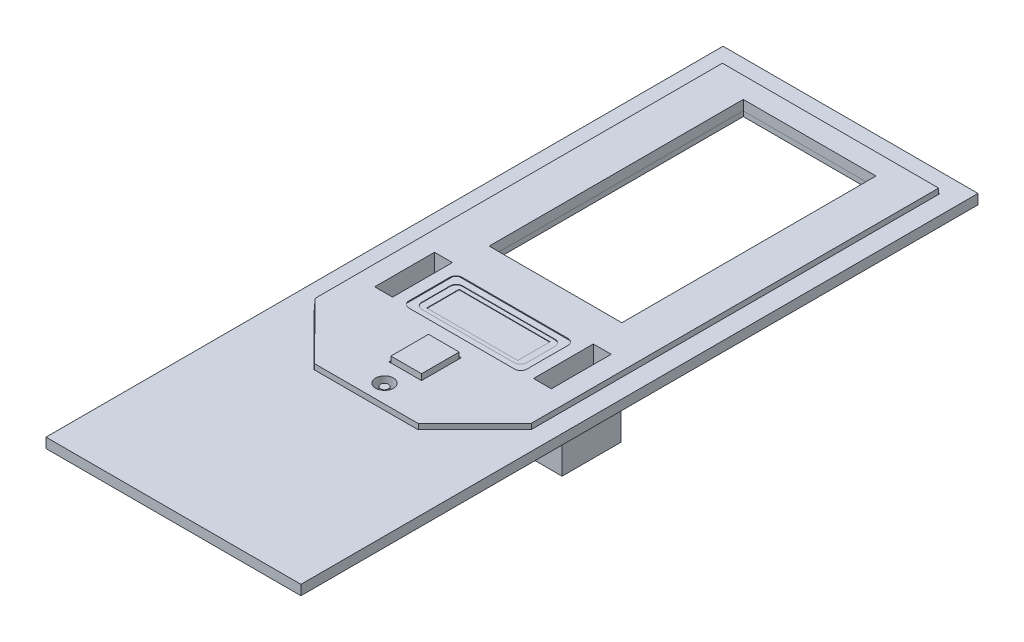
SolidWorks part; units mm, degrees
other "Main"
other "secondary"
other "mainDoorPanel"
other "secondaryPanel"
ref_plane "Front Plane" through (0, 0, 0) normal (0, 0, 1) x (1, 0, 0)
ref_plane "Top Plane" through (0, 0, 0) normal (0, 1, 0) x (1, 0, 0)
ref_plane "Right Plane" through (0, 0, 0) normal (1, 0, 0) x (0, 0, -1)
sketch "Sketch1" plane through (0, 0, 0) normal (0, 1, 0) x (1, 0, 0)
  line L1 (-31.4334, 64.5752) -> (19.899, 64.5752)
  line L2 (-31.4334, 64.5752) -> (-31.4334, -71.7502)
  line L3 (-31.4334, -71.7502) -> (19.899, -71.7502)
  line L4 (19.899, 64.5752) -> (19.899, -71.7502)
  dimension "D1" = 136.3254
  dimension "D2" = 51.3324
extrude "Boss-Extrude1" add sketch "Sketch1" along normal blind 2
sketch "Sketch2" plane through (0, 2, 0) normal (0, 1, 0) x (1, 0, 0)
  line L2 (-27.5414, -30.4459) -> (-27.5414, 60.5429)
  line L3 (-27.5414, 60.5429) -> (16.007, 60.5429)
  line L4 (16.007, -30.4459) -> (16.007, 60.5429)
  line L5 (19.899, -71.7502) -> (19.899, 64.5752) construction
  line L6 (-31.4334, 64.5752) -> (-31.4334, -71.7502) construction
  line L7 (19.899, 64.5752) -> (-31.4334, 64.5752) construction
  line L8 (-16.2134, -41.6661) -> (4.679, -41.6661)
  line L9 (16.007, -30.4459) -> (4.679, -41.6661)
  line L10 (-16.2134, -41.6661) -> (-27.5414, -30.4459)
  dimension "D2" = 3.892
  dimension "D3" = 3.892
  dimension "D4" = 43.5484
  dimension "D5" = 4.0323
  dimension "D6" = 15.22
  dimension "D8" = 15.22
extrude "Cut-Extrude1" cut sketch "Sketch2" against normal blind 1
sketch "Sketch3" plane through (0, 1, 0) normal (0, 1, 0) x (1, 0, 0)
  line L1 (-19.1263, 56.3354) -> (7.5918, 56.3354)
  line L2 (-19.1263, 56.3354) -> (-19.1263, 5.1745)
  line L3 (-19.1263, 5.1745) -> (7.5918, 5.1745)
  line L4 (7.5918, 56.3354) -> (7.5918, 5.1745)
extrude "Cut-Extrude2" cut sketch "Sketch3" against normal blind 1
sketch "Sketch4" plane through (0, 1, 0) normal (0, 1, 0) x (1, 0, 0)
  line L0 (-19.1263, 5.1745) -> (7.5918, 5.1745) construction
  line L1 (-16.0968, -1.1859) -> (4.5624, -1.1859)
  line L2 (-16.0968, -1.1859) -> (-16.0968, -14.7904)
  line L3 (-16.0968, -14.7904) -> (4.5624, -14.7904)
  line L4 (4.5624, -1.1859) -> (4.5624, -14.7904)
  dimension "D1" = 13.6045
  dimension "D2" = 20.6592
  dimension "D3" = 6.3604
extrude "Boss-Extrude2" add sketch "Sketch4" along normal blind 1
sketch "Sketch5" plane through (0, 1, 0) normal (0, 1, 0) x (1, 0, 0)
  line L0 (-27.5414, 60.5429) -> (-27.5414, -30.4459) construction
  line L1 (-18.4951, 0) -> (-25.0169, 0)
  line L2 (-18.4951, 0) -> (-18.4951, -14.8535)
  line L3 (-18.4951, -14.8535) -> (-25.0169, -14.8535)
  line L4 (-25.0169, 0) -> (-25.0169, -14.8535)
  line L5 (6.9607, -14.8535) -> (13.4824, -14.8535)
  line L6 (6.9607, -14.8535) -> (6.9607, 0.7912)
  line L7 (6.9607, 0.7912) -> (13.4824, 0.7912)
  line L8 (13.4824, -14.8535) -> (13.4824, 0.7912)
  line L9 (16.007, -30.4459) -> (16.007, 60.5429) construction
  line L10 (-16.0968, -14.7904) -> (4.5624, -14.7904) construction
  dimension "D1" = 6.5217
  dimension "D2" = 6.5217
  dimension "D3" = 2.5245
  dimension "D4" = 2.5245
  dimension "D5" = 0.0631
  dimension "D6" = 0.0631
extrude "Cut-Extrude3" cut sketch "Sketch5" against normal blind 1
sketch "Sketch6" plane through (0, 1, 0) normal (0, 1, 0) x (1, 0, 0)
  line L0 (-5.7672, -14.7904) -> (-5.7672, -41.6661) construction
  line L1 (-8.8528, -17.315) -> (-2.6817, -17.315)
  line L2 (-8.8528, -17.315) -> (-8.8528, -24.8886)
  line L3 (-8.8528, -24.8886) -> (-2.6817, -24.8886)
  line L4 (-2.6817, -17.315) -> (-2.6817, -24.8886)
  line L5 (-16.0968, -14.7904) -> (4.5624, -14.7904) construction
  line L6 (-16.2134, -41.6661) -> (4.679, -41.6661) construction
  line L7 (-16.0968, -14.7904) -> (4.5624, -14.7904) construction
  dimension "D1" = 7.5736
  dimension "D2" = 6.1711
  dimension "D3" = 3.0856
  dimension "D4" = 2.5245
extrude "Cut-Extrude4" cut sketch "Sketch6" against normal blind 1
sketch "Sketch7" plane through (0, 1, 0) normal (0, 1, 0) x (1, 0, 0)
  line L0 (-8.8528, -24.8886) -> (-2.6817, -24.8886) construction
  circle A0 centre (-5.7672, -29.2505) radius 2.4895
  dimension "D1" = 4.3619
extrude "Cut-Extrude5" cut sketch "Sketch7" against normal blind 1
sketch "Sketch8" plane through (0, 1, 0) normal (0, 1, 0) x (1, 0, 0)
  line L6 (-27.5414, -21.4805) -> (-27.5414, -30.4459)
  line L8 (-27.5414, -30.4459) -> (-16.2134, -41.6661)
  line L10 (-16.2134, -41.6661) -> (4.679, -41.6661)
  line L16 (4.679, -41.6661) -> (16.007, -30.4459)
  line L18 (16.007, -30.4459) -> (16.007, -21.4805)
  line L22 (4.6739, -32.9033) -> (16.007, -21.4805)
  line L23 (16.007, -30.4459) -> (16.007, 60.5429) construction
  line L24 (-16.2083, -32.9033) -> (-27.5414, -21.4805)
  line L25 (-27.5414, 60.5429) -> (-27.5414, -30.4459) construction
  line L26 (4.6739, -32.9033) -> (-16.2083, -32.9033)
extrude "Boss-Extrude3" add sketch "Sketch8" along normal blind 1
sketch "Sketch9" plane through (0, 1, 0) normal (0, 1, 0) x (1, 0, 0)
  line L1 (-8.8528, -24.8886) -> (-2.6817, -24.8886)
  line L2 (-8.8528, -24.8886) -> (-8.8528, -17.315)
  line L3 (-8.8528, -17.315) -> (-2.6817, -17.315)
  line L4 (-2.6817, -24.8886) -> (-2.6817, -17.315)
sketch "Sketch10" plane through (0, 0, 0) normal (0, -1, 0) x (1, 0, 0)
  line L1 (-8.8528, 24.8886) -> (-2.6817, 24.8886)
  line L2 (-8.8528, 24.8886) -> (-8.8528, 17.315)
  line L3 (-8.8528, 17.315) -> (-2.6817, 17.315)
  line L4 (-2.6817, 24.8886) -> (-2.6817, 17.315)
extrude "Boss-Extrude4" add sketch "Sketch10" against normal blind 4
sketch "Sketch11" plane through (0, 1, 0) normal (0, 1, 0) x (1, 0, 0)
  line L0 (-27.5414, 60.5429) -> (16.007, 60.5429)
  line L1 (16.007, 60.5429) -> (16.007, -21.4805)
  line L2 (16.007, -21.4805) -> (4.6739, -32.9033)
  line L3 (4.6739, -32.9033) -> (-16.2083, -32.9033)
  line L4 (-16.2083, -32.9033) -> (-27.5414, -21.4805)
  line L5 (-27.5414, -21.4805) -> (-27.5414, 60.5429)
extrude "Boss-Extrude5" add sketch "Sketch11" along normal blind 2 separate body
sketch "Sketch12" plane through (0, 3, 0) normal (0, 1, 0) x (1, 0, 0)
  line L0 (-8.8528, -17.315) -> (-2.6817, -17.315) construction
  line L1 (-9.0528, -17.115) -> (-2.4817, -17.115)
  line L2 (-9.0528, -17.115) -> (-9.0528, -25.0886)
  line L3 (-9.0528, -25.0886) -> (-2.4817, -25.0886)
  line L4 (-2.4817, -17.115) -> (-2.4817, -25.0886)
  line L5 (-8.8528, -24.8886) -> (-8.8528, -17.315) construction
  line L6 (-2.6817, -24.8886) -> (-8.8528, -24.8886) construction
  line L7 (-2.6817, -17.315) -> (-2.6817, -24.8886) construction
  dimension "D1" = 0.2
  dimension "D2" = 0.2
  dimension "D3" = 0.2
  dimension "D4" = 0.2
extrude "Cut-Extrude6" cut sketch "Sketch12" against normal blind 2
sketch "Sketch13" plane through (0, 1, 0) normal (0, -1, 0) x (1, 0, 0)
  line L1 (-19.1263, -5.1745) -> (7.5918, -5.1745)
  line L2 (-19.1263, -5.1745) -> (-19.1263, -56.3354)
  line L3 (-19.1263, -56.3354) -> (7.5918, -56.3354)
  line L4 (7.5918, -5.1745) -> (7.5918, -56.3354)
  circle A0 centre (-5.7672, 29.2505) radius 1.8
extrude "Cut-Extrude9" cut sketch "Sketch13" against normal blind 2
sketch "Sketch14" plane through (0, 1, 0) normal (0, -1, 0) x (1, 0, 0)
  circle A0 centre (-5.7672, 29.2505) radius 2.2
  circle A1 centre (-5.7672, 29.2505) radius 1.8
extrude "Boss-Extrude11" add sketch "Sketch14" along normal blind 2 separate body
combine bodies "Combine1" operation type add bodies to combine 120 114
sketch "Sketch17" plane through (0, -1, 0) normal (0, -1, 0) x (1, 0, 0)
  circle A0 centre (-5.7672, 29.2505) radius 2.2
extrude "Boss-Extrude12" add sketch "Sketch17" along normal blind 1
sketch "Sketch18" plane through (0, -1, 0) normal (0, 1, 0) x (1, 0, 0)
  circle A0 centre (-5.7672, -29.2505) radius 0.8
extrude "Boss-Extrude15" add sketch "Sketch18" along normal blind 3.4 separate body
combine bodies "Combine3" operation type add bodies to combine 122 126
sketch "Sketch20" plane through (0, 1, 0) normal (0, -1, 0) x (1, 0, 0)
  line L0 (-21.756, 14.8535) -> (-21.756, 0) construction
  line L1 (-24.556, 14.4535) -> (-18.956, 14.4535)
  line L2 (-24.556, 14.4535) -> (-24.556, 0.4)
  line L3 (-24.556, 0.4) -> (-18.956, 0.4)
  line L4 (-18.956, 14.4535) -> (-18.956, 0.4)
  line L5 (7.4216, -0.3912) -> (13.0216, -0.3912)
  line L6 (7.4216, -0.3912) -> (7.4216, 14.4535)
  line L7 (7.4216, 14.4535) -> (13.0216, 14.4535)
  line L8 (13.0216, -0.3912) -> (13.0216, 14.4535)
  line L9 (-25.0169, 14.8535) -> (-18.4951, 14.8535) construction
  line L10 (-18.4951, 0) -> (-25.0169, 0) construction
  line L11 (10.2216, 14.8535) -> (10.2216, -0.7912) construction
  line L12 (6.9607, 14.8535) -> (13.4824, 14.8535) construction
  line L13 (13.4824, -0.7912) -> (6.9607, -0.7912) construction
  dimension "D1" = 2.8
  dimension "D2" = 2.8
  dimension "D3" = 2.8
  dimension "D4" = 2.8
  dimension "D5" = 0.4
  dimension "D6" = 0.4
  dimension "D7" = 0.4
  dimension "D8" = 0.4
extrude "Extrude-Thin3" add sketch "Sketch20" along normal blind 13.324 separate body thin thin type one direction reverse wall 1
sketch "Sketch26" plane through (0, 1, 0) normal (0, -1, 0) x (1, 0, 0)
  line L1 (-23.556, 13.4535) -> (-19.956, 13.4535)
  line L2 (-23.556, 13.4535) -> (-23.556, 1.4)
  line L3 (-23.556, 1.4) -> (-19.956, 1.4)
  line L4 (-19.956, 13.4535) -> (-19.956, 1.4)
  line L5 (8.4216, 0.6088) -> (12.0216, 0.6088)
  line L6 (8.4216, 0.6088) -> (8.4216, 13.4535)
  line L7 (8.4216, 13.4535) -> (12.0216, 13.4535)
  line L8 (12.0216, 0.6088) -> (12.0216, 13.4535)
extrude "Cut-Extrude12" cut sketch "Sketch26" against normal blind 13.324
sketch "Sketch27" plane through (0, -12.324, 0) normal (0, -1, 0) x (1, 0, 0)
  line L0 (7.4216, -0.3912) -> (13.0216, -0.3912) construction
  line L1 (-24.556, 14.4535) -> (-18.956, 14.4535)
  line L2 (-24.556, 14.4535) -> (-24.556, 0.4)
  line L3 (-24.556, 0.4) -> (-18.956, 0.4)
  line L4 (-18.956, 14.4535) -> (-18.956, 0.4)
  line L5 (7.4216, 14.4535) -> (12.992, 14.4535)
  line L6 (7.4216, 14.4535) -> (7.4216, -0.3912)
  line L7 (7.4216, -0.3912) -> (12.992, -0.3912)
  line L8 (12.992, 14.4535) -> (12.992, -0.3912)
extrude "Boss-Extrude18" add sketch "Sketch27" against normal blind 1 separate body
combine bodies "Combine4" operation type add bodies to combine 134 135 136 137 138
sketch "Sketch28" plane through (0, 2, 0) normal (0, 1, 0) x (1, 0, 0)
  line L1 (-16.0968, -1.1859) -> (4.5624, -1.1859)
  line L2 (-16.0968, -1.1859) -> (-16.0968, -14.7904)
  line L3 (-16.0968, -14.7904) -> (4.5624, -14.7904)
  line L4 (4.5624, -1.1859) -> (4.5624, -14.7904)
extrude "Cut-Extrude13" cut sketch "Sketch28" against normal up to surface (1 mm away) up to face at (-5.7672, 1, 31.7399)
sketch "Sketch29" plane through (0, 3, 0) normal (0, 1, 0) x (1, 0, 0)
  line L0 (8.4216, -13.4535) -> (8.4216, -0.6088) construction
  line L1 (-17.656, -2.9778) -> (6.1216, -2.9778)
  line L2 (-17.656, -2.9778) -> (-17.656, -13.706)
  line L3 (-17.656, -13.706) -> (6.1216, -13.706)
  line L4 (6.1216, -2.9778) -> (6.1216, -13.706)
  line L5 (-19.956, -1.4) -> (-19.956, -13.4535) construction
  line L6 (12.0216, -13.4535) -> (8.4216, -13.4535) construction
  line L7 (-23.556, -1.4) -> (-19.956, -1.4) construction
  dimension "D1" = 2.3
  dimension "D2" = 2.3
  dimension "D3" = 0.2525
  dimension "D4" = 1.5778
extrude "Cut-Extrude15" cut sketch "Sketch29" against normal blind 10
sketch "Sketch30" plane through (0, 1, 0) normal (0, 1, 0) x (1, 0, 0)
  line L1 (-17.656, -2.9778) -> (6.1216, -2.9778)
  line L2 (-17.656, -2.9778) -> (-17.656, -13.706)
  line L3 (-17.656, -13.706) -> (6.1216, -13.706)
  line L4 (6.1216, -2.9778) -> (6.1216, -13.706)
  line L5 (-16.3236, -4.2401) -> (4.7892, -4.2401)
  line L6 (-16.3236, -4.2401) -> (-16.3236, -12.4437)
  line L7 (-16.3236, -12.4437) -> (4.7892, -12.4437)
  line L8 (4.7892, -4.2401) -> (4.7892, -12.4437)
  dimension "D1" = 1.3324
  dimension "D2" = 1.3324
  dimension "D3" = 1.2623
  dimension "D4" = 1.2623
extrude "Boss-Extrude20" add sketch "Sketch30" along normal blind 1.8 separate body
sketch "Sketch31" plane through (0, 1, 0) normal (0, 1, 0) x (1, 0, 0)
  line L1 (-16.3236, -4.2401) -> (4.7892, -4.2401)
  line L2 (-16.3236, -4.2401) -> (-16.3236, -12.4437)
  line L3 (-16.3236, -12.4437) -> (4.7892, -12.4437)
  line L4 (4.7892, -4.2401) -> (4.7892, -12.4437)
extrude "Boss-Extrude21" add sketch "Sketch31" along normal blind 1.6 separate body
combine bodies "Combine5" operation type add bodies to combine 140 145 146
sketch "Sketch35" plane through (0, 1, 0) normal (0, -1, 0) x (1, 0, 0)
  line L8 (6.2216, 2.8778) -> (6.2216, 13.806)
  line L9 (6.2216, 13.806) -> (-17.756, 13.806)
  line L10 (-17.756, 13.806) -> (-17.756, 2.8778)
  line L11 (-17.756, 2.8778) -> (6.2216, 2.8778)
  line L12 (6.2216, 2.8778) -> (6.2216, 13.806)
  line L13 (6.2216, 13.806) -> (-17.756, 13.806)
  line L14 (-17.756, 13.806) -> (-17.756, 2.8778)
  line L15 (-17.756, 2.8778) -> (6.2216, 2.8778)
  dimension "D1" = 0.1
extrude "Cut-Extrude21" cut sketch "Sketch35" against normal blind 1.9
fillet "Fillet2" radius 1.25 4 edges at (-17.656, 2.95, 13.706) (6.1216, 2.95, 13.706) (6.1216, 2.95, 2.9778) (-17.656, 2.95, 2.9778)
fillet "Fillet3" radius 1.25 4 edges at (4.7892, 2.7, 12.4437) (4.7892, 2.7, 4.2401) (-16.3236, 2.7, 12.4437) (-16.3236, 2.7, 4.2401)
sketch "Sketch37" plane through (0, 2.6, 0) normal (0, 1, 0) x (1, 0, 0)
  line L4 (3.5392, -4.2401) -> (-15.0736, -4.2401) construction
  line L5 (-14.9211, -5.0781) -> (3.3866, -5.0781)
  line L6 (-14.9211, -5.0781) -> (-14.9211, -11.6057)
  line L7 (-14.9211, -11.6057) -> (3.3866, -11.6057)
  line L8 (3.3866, -5.0781) -> (3.3866, -11.6057)
  line L9 (-16.3236, -5.4901) -> (-16.3236, -11.1937) construction
  line L10 (4.7892, -11.1937) -> (4.7892, -5.4901) construction
  line L11 (-15.0736, -12.4437) -> (3.5392, -12.4437) construction
  dimension "D1" = 0.838
  dimension "D2" = 1.4025
  dimension "D3" = 1.4025
  dimension "D4" = 0.838
extrude "Cut-Extrude22" cut sketch "Sketch37" against normal blind 0.1
sketch "Sketch41" plane through (0, 2.6, 0) normal (0, 1, 0) x (1, 0, 0)
  line L5 (-14.9211, -5.0781) -> (3.3866, -5.0781)
  line L6 (-14.9211, -5.0781) -> (-14.9211, -11.6057)
  line L7 (-14.9211, -11.6057) -> (3.3866, -11.6057)
  line L8 (-15.0736, -12.4437) -> (3.5392, -12.4437)
  line L9 (4.7892, -11.1937) -> (4.7892, -5.4901)
  line L10 (3.5392, -4.2401) -> (-15.0736, -4.2401)
  line L11 (-16.3236, -5.4901) -> (-16.3236, -11.1937)
  line L12 (-15.0736, -12.4437) -> (3.5392, -12.4437)
  line L13 (4.7892, -11.1937) -> (4.7892, -5.4901)
  line L14 (3.5392, -4.2401) -> (-15.0736, -4.2401)
  line L15 (-16.3236, -5.4901) -> (-16.3236, -11.1937)
  line L16 (3.3866, -5.0781) -> (3.3866, -11.6057)
  arc A8 (3.5392, -12.4437) -> (4.7892, -11.1937) centre (3.5392, -11.1937) ccw
  arc A9 (4.7892, -5.4901) -> (3.5392, -4.2401) centre (3.5392, -5.4901) ccw
  arc A10 (-15.0736, -4.2401) -> (-16.3236, -5.4901) centre (-15.0736, -5.4901) ccw
  arc A11 (-16.3236, -11.1937) -> (-15.0736, -12.4437) centre (-15.0736, -11.1937) ccw
  arc A12 (3.5392, -12.4437) -> (4.7892, -11.1937) centre (3.5392, -11.1937) ccw
  arc A13 (4.7892, -5.4901) -> (3.5392, -4.2401) centre (3.5392, -5.4901) ccw
  arc A14 (-15.0736, -4.2401) -> (-16.3236, -5.4901) centre (-15.0736, -5.4901) ccw
  arc A15 (-16.3236, -11.1937) -> (-15.0736, -12.4437) centre (-15.0736, -11.1937) ccw
  dimension "D1" = 0
extrude "Boss-Extrude27" add sketch "Sketch41" along normal blind 0.1 separate body
combine bodies "Combine6" operation type add bodies to combine 160 154
sketch "Sketch43" plane through (0, 2.5, 0) normal (0, 1, 0) x (1, 0, 0)
  line L1 (-14.9211, -5.0781) -> (3.3866, -5.0781)
  line L2 (-14.9211, -5.0781) -> (-14.9211, -11.6057)
  line L3 (-14.9211, -11.6057) -> (3.3866, -11.6057)
  line L4 (3.3866, -5.0781) -> (3.3866, -11.6057)
extrude "Boss-Extrude28" add sketch "Sketch43" along normal blind 0.1 separate body
combine bodies "Combine7" operation type add bodies to combine 162 161
sketch "Sketch50" plane through (13.0216, 0, 0) normal (1, 0, 0) x (0, 0, -1)
  line L0 (-14.4535, 1) -> (-11.2935, -2.16)
  line L1 (0.3912, 1) -> (-14.4535, 1) construction
  line L2 (-14.4535, -12.324) -> (-14.4535, 1) construction
  line L3 (-11.2935, -2.16) -> (-11.2935, -12.324)
  line L4 (0.3912, -12.324) -> (-14.4535, -12.324) construction
  line L5 (-11.2935, -12.324) -> (-14.4535, -12.324)
  line L6 (-14.4535, -12.324) -> (-14.4535, 1)
  dimension "D1" = 3.16
  dimension "D2" = 3.16
extrude "Cut-Extrude24" cut sketch "Sketch50" against normal blind 40.1
sketch "Sketch51" plane through (0, -6.7268, 6.7268) normal (0, -0.7071, 0.7071) x (1, 0, 0)
  line L1 (7.4216, 10.9273) -> (13.0216, 10.9273)
  line L2 (7.4216, 10.9273) -> (7.4216, 6.4584)
  line L3 (7.4216, 6.4584) -> (13.0216, 6.4584)
  line L4 (13.0216, 10.9273) -> (13.0216, 6.4584)
  line L5 (-18.956, 10.9273) -> (-24.556, 10.9273)
  line L6 (-18.956, 10.9273) -> (-18.956, 6.4584)
  line L7 (-18.956, 6.4584) -> (-24.556, 6.4584)
  line L8 (-24.556, 10.9273) -> (-24.556, 6.4584)
extrude "Boss-Extrude29" add sketch "Sketch51" along normal blind 1 separate body
sketch "Sketch52" plane through (0, 7.7268, 7.7268) normal (0, 0.7071, 0.7071) x (1, 0, 0)
  line L1 (7.4216, -9.5131) -> (13.0216, -9.5131)
  line L2 (7.4216, -9.5131) -> (7.4216, -10.5131)
  line L3 (7.4216, -10.5131) -> (13.0216, -10.5131)
  line L4 (13.0216, -9.5131) -> (13.0216, -10.5131)
  line L5 (-24.556, -9.5131) -> (-18.956, -9.5131)
  line L6 (-24.556, -9.5131) -> (-24.556, -10.5131)
  line L7 (-24.556, -10.5131) -> (-18.956, -10.5131)
  line L8 (-18.956, -9.5131) -> (-18.956, -10.5131)
extrude "Boss-Extrude30" add sketch "Sketch52" along normal blind 2.5 separate body
combine bodies "Combine8" operation type add bodies to combine 167 168 169 170 171
sketch "Sketch53" plane through (0, 0, 11.2935) normal (0, 0, 1) x (1, 0, 0)
  line L0 (-24.556, -12.324) -> (-24.556, -2.16) construction
  line L1 (-24.556, -11.324) -> (-18.956, -11.324)
  line L2 (-24.556, -11.324) -> (-24.556, -12.324)
  line L3 (-24.556, -12.324) -> (-18.956, -12.324)
  line L4 (-18.956, -11.324) -> (-18.956, -12.324)
  line L5 (7.4216, -12.324) -> (7.4216, -2.16) construction
  line L6 (13.0216, -12.324) -> (7.4216, -12.324)
  line L7 (13.0216, -12.324) -> (13.0216, -11.324)
  line L8 (13.0216, -11.324) -> (7.4216, -11.324)
  line L9 (7.4216, -12.324) -> (7.4216, -11.324)
  line L10 (8.4216, -11.324) -> (12.0216, -11.324) construction
  line L11 (-23.556, -11.324) -> (-19.956, -11.324) construction
  dimension "D1" = 0
  dimension "D2" = 0
extrude "Boss-Extrude31" add sketch "Sketch53" along normal blind 1
sketch "Sketch54" plane through (0, -11.324, 0) normal (0, 1, 0) x (1, 0, 0)
  line L1 (-24.556, -11.2935) -> (-18.956, -11.2935)
  line L2 (-24.556, -11.2935) -> (-24.556, -12.2935)
  line L3 (-24.556, -12.2935) -> (-18.956, -12.2935)
  line L4 (-18.956, -11.2935) -> (-18.956, -12.2935)
  line L5 (7.4216, -11.2935) -> (13.0216, -11.2935)
  line L6 (7.4216, -11.2935) -> (7.4216, -12.2935)
  line L7 (7.4216, -12.2935) -> (13.0216, -12.2935)
  line L8 (13.0216, -11.2935) -> (13.0216, -12.2935)
extrude "Boss-Extrude32" add sketch "Sketch54" along normal up to body separate body
combine bodies "Combine9" operation type add bodies to combine 173 174 175
sketch "Sketch55" plane through (0, -11.324, 0) normal (0, 1, 0) x (1, 0, 0)
  line L0 (12.0216, -0.6088) -> (12.0216, -13.4535) construction
  line L1 (12.0216, -1.4) -> (8.4216, -1.4)
  line L2 (12.0216, -1.4) -> (12.0216, -0.6088)
  line L3 (12.0216, -0.6088) -> (8.4216, -0.6088)
  line L4 (8.4216, -1.4) -> (8.4216, -0.6088)
  line L5 (-23.556, -1.4) -> (-19.956, -1.4) construction
  dimension "D1" = 0
extrude "Boss-Extrude33" add sketch "Sketch55" along normal up to surface (14.324 mm away) separate body up to face at (-5.7672, 3, 8.3419)
sketch "Sketch56" plane through (7.4216, 0, 0) normal (-1, 0, 0) x (0, 0, 1)
  line L1 (0.4, -12.324) -> (-0.3912, -12.324)
  line L2 (0.4, -12.324) -> (0.4, 1)
  line L3 (0.4, 1) -> (-0.3912, 1)
  line L4 (-0.3912, -12.324) -> (-0.3912, 1)
extrude "Cut-Extrude25" cut sketch "Sketch56" against normal up to surface (5.6 mm away) up to face at (13.0216, -5.0444, 7.9345)
sketch "Sketch58" plane through (0, 1, 0) normal (0, 1, 0) x (1, 0, 0)
  line L12 (-16.2083, -32.9033) -> (4.6739, -32.9033)
  line L13 (4.6739, -32.9033) -> (16.007, -21.4805)
  line L14 (16.007, -21.4805) -> (16.007, 60.5429)
  line L15 (16.007, 60.5429) -> (-27.5414, 60.5429)
  line L16 (-27.5414, 60.5429) -> (-27.5414, -21.4805)
  line L17 (-27.5414, -21.4805) -> (-16.2083, -32.9033)
  line L18 (-16.2083, -32.9033) -> (4.6739, -32.9033)
  line L19 (4.6739, -32.9033) -> (16.007, -21.4805)
  line L20 (16.007, -21.4805) -> (16.007, 60.5429)
  line L21 (16.007, 60.5429) -> (-27.5414, 60.5429)
  line L22 (-27.5414, 60.5429) -> (-27.5414, -21.4805)
  line L23 (-27.5414, -21.4805) -> (-16.2083, -32.9033)
  dimension "D1" = 0
extrude "Cut-Extrude-Thin1" cut sketch "Sketch58" along normal up to surface (1 mm away) thin up to face at (-5.7672, 2, -2.053) thin type one direction wall 0.1
